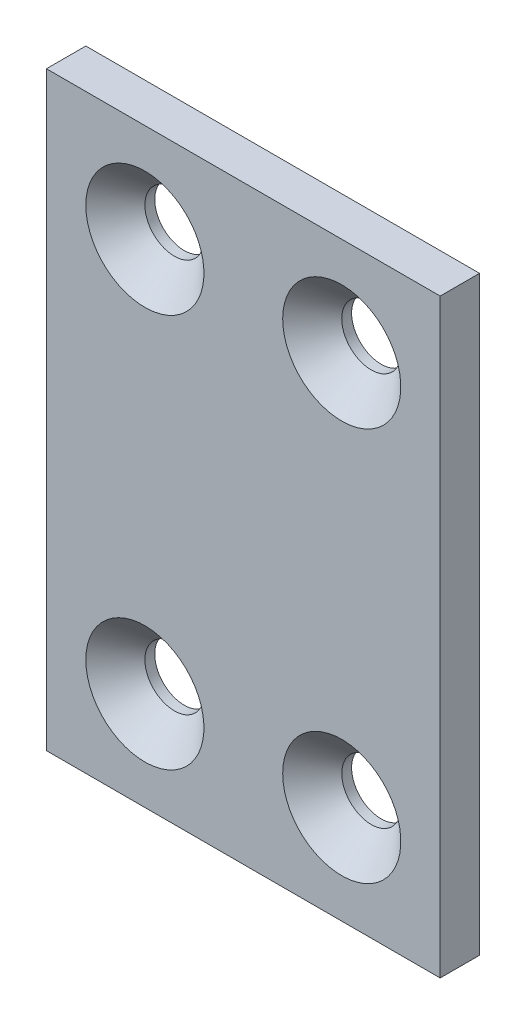
SolidWorks part; units mm, degrees
ref_plane "Front Plane" through (0, 0, 0) normal (0, 0, 1) x (1, 0, 0)
ref_plane "Top Plane" through (0, 0, 0) normal (0, 1, 0) x (1, 0, 0)
ref_plane "Right Plane" through (0, 0, 0) normal (1, 0, 0) x (0, 0, -1)
sketch "Sketch1" plane through (0, 0, 0) normal (0, 0, 1) x (1, 0, 0)
  line L1 (-20, -30) -> (20, -30)
  line L2 (-20, -30) -> (-20, 30)
  line L3 (-20, 30) -> (20, 30)
  line L4 (20, -30) -> (20, 30)
  line L5 (-20, -30) -> (20, 30) construction
  line L6 (-20, 30) -> (20, -30) construction
  point P0 (0, 0)
  dimension "D2" = 40
  dimension "D3" = 60
extrude "Boss-Extrude1" add sketch "Sketch1" along normal mid plane 4
sketch "Sketch2" plane through (0, 0, 2) normal (0, 0, 1) x (1, 0, 0)
  line L0 (-10, 20) -> (-10, -20) construction
  line L1 (-10, -20) -> (10, -20) construction
  line L2 (10, -20) -> (10, 20) construction
  line L3 (10, 20) -> (-10, 20) construction
  line L4 (-10, 20) -> (10, -20) construction
  circle A0 centre (-10, 20) radius 3
  circle A1 centre (10, 20) radius 3
  circle A2 centre (-10, -20) radius 3
  circle A3 centre (10, -20) radius 3
  point P8 (0, 0)
  dimension "D1" = 6
  dimension "D2" = 40
  dimension "D3" = 20
extrude "Cut-Extrude1" cut sketch "Sketch2" against normal through all
chamfer "Chamfer1" distance 3 angle 45 4 edges at (13, -20, 2) (-7, -20, 2) (13, 20, 2) (-7, 20, 2)
fillet "Fillet1" [suppressed] radius 1
